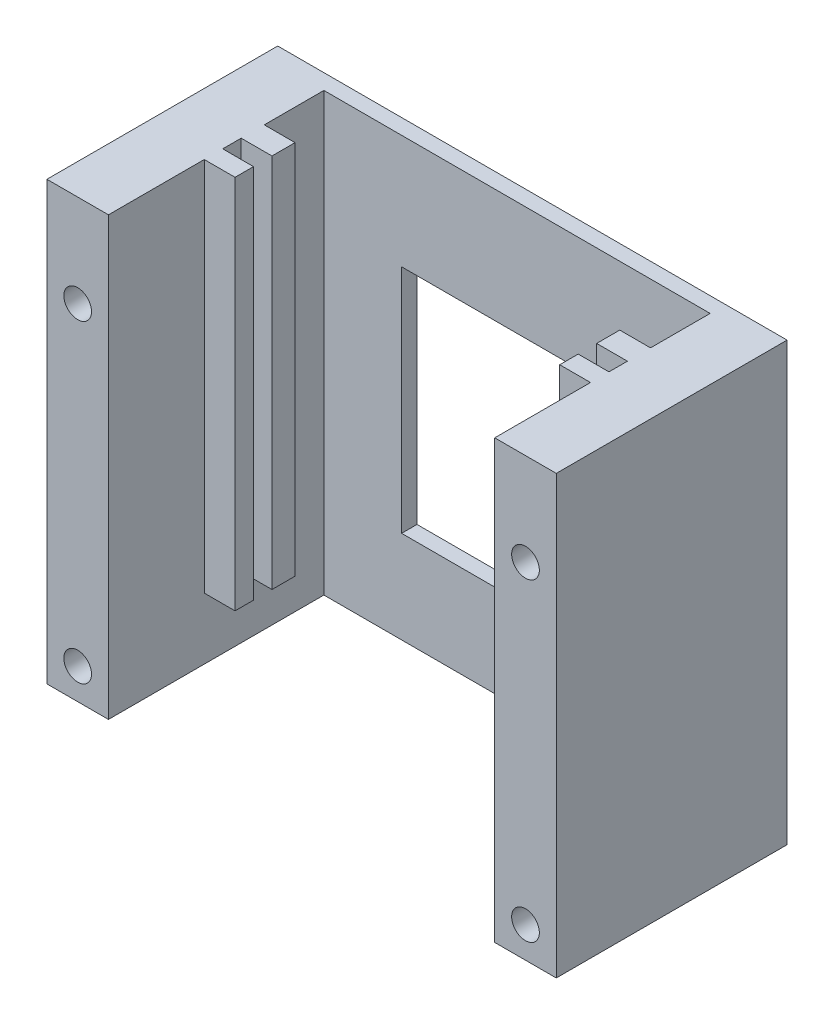
SolidWorks part; units mm, degrees
ref_plane "Plan de face" through (0, 0, 0) normal (0, 0, 1) x (1, 0, 0)
ref_plane "Plan de dessus" through (0, 0, 0) normal (0, 1, 0) x (1, 0, 0)
ref_plane "Plan de droite" through (0, 0, 0) normal (1, 0, 0) x (0, 0, -1)
sketch "Esquisse1" plane through (0, 0, 0) normal (0, 0, 1) x (1, 0, 0)
  line L0 (0, 0) -> (0, -27) construction
  line L1 (0, -27) -> (0, 30) construction
  line L2 (0, 0) -> (25.4165, -15.9375) construction
  line L3 (25.4165, -15.9375) -> (-22.8748, 14.3437) construction
  line L4 (-25.4165, -15.9375) -> (0, 0) construction
  line L5 (0, 0) -> (22.8748, 14.3437) construction
  line L6 (0, 30) -> (25.4165, -15.9375) construction
  line L8 (12.5, -14) -> (-12.5, -14)
  line L9 (12.5, -14) -> (12.5, -17)
  line L10 (12.5, -17) -> (-12.5, -17)
  line L11 (-12.5, -14) -> (-12.5, -17)
  circle A0 centre (0, 0) radius 37
  circle A1 centre (0, 30) radius 1.5
  circle A2 centre (-22.8748, 14.3437) radius 1.5
  circle A3 centre (-25.4165, -15.9375) radius 1.5
  circle A4 centre (0, -27) radius 1.5
  circle A5 centre (25.4165, -15.9375) radius 1.5
  circle A6 centre (22.8748, 14.3437) radius 1.5
  dimension "D1" = 74
  dimension "D11" = 3
  dimension "D12" = 3
  dimension "D13" = 3
  dimension "D14" = 3
  dimension "D15" = 3
  dimension "D16" = 3
  dimension "D2" = 27
  dimension "D3" = 57
  dimension "D4" = 57
  dimension "D5" = 30
  dimension "D6" = 30
  dimension "D7" = 27
  dimension "D8" = 52.5
  dimension "D9" = 52.5
  dimension "D10" = 47.25
  dimension "D17" = 25
  dimension "D18" = 3
  dimension "D19" = 10
  dimension "D20" = 12.5
extrude "Boss.-Extru.1" add sketch "Esquisse1" along normal blind 2
sketch "Esquisse2" plane through (0, 0, 0) normal (0, 0, -1) x (-1, 0, 0)
  line L0 (-16.55, 14.9) -> (-16.55, -13.5)
  line L1 (-12.55, 14.9) -> (12.55, 14.9)
  line L2 (-12.55, 14.9) -> (-12.55, -9.5)
  line L3 (-12.55, -9.5) -> (12.55, -9.5)
  line L4 (12.55, 14.9) -> (12.55, -9.5)
  line L5 (-16.55, -13.5) -> (16.55, -13.5)
  line L6 (16.55, -13.5) -> (16.55, 14.9)
  line L7 (16.55, 14.9) -> (12.55, 14.9)
  line L8 (-16.55, 14.9) -> (-12.55, 14.9)
  point P0 (0, 0)
  dimension "D1" = 25.1
  dimension "D2" = 9.5
  dimension "D3" = 24.4
  dimension "D4" = 4
  dimension "D5" = 4
  dimension "D6" = 4
  dimension "D7" = 12.55
extrude "Boss.-Extru.2" add sketch "Esquisse2" along normal blind 15 contours L8 L0 L5 L6 L7 L4 L3 L2 region at (14.55, 14.4639, 0)
sketch "Esquisse3" plane through (-12.55, 0, 0) normal (1, 0, 0) x (0, 0, -1)
  line L0 (15, 14.9) -> (0, 14.9) construction
  line L1 (10.125, 14.9) -> (8.625, 14.9)
  line L2 (10.125, 14.9) -> (10.125, -13.5)
  line L3 (10.125, -13.5) -> (8.625, -13.5)
  line L4 (8.625, 14.9) -> (8.625, -13.5)
  line L5 (15, -13.5) -> (0, -13.5) construction
  line L6 (0, 14.9) -> (7.5, 14.9) construction
  line L8 (6.225, 14.9) -> (7.425, 14.9)
  line L9 (6.225, 14.9) -> (6.225, -13.5)
  line L10 (6.225, -13.5) -> (7.425, -13.5)
  line L11 (7.425, 14.9) -> (7.425, -13.5)
  line L12 (8, 14.9) -> (8, -13.5) construction
  dimension "D1" = 1.5
  dimension "D2" = 0.625
  dimension "D3" = 1.2
  dimension "D4" = 1.2
  dimension "D5" = 0.575
  dimension "D6" = 0.5
extrude "Boss.-Extru.3" add sketch "Esquisse3" along normal blind 2 contours L11 L10 L9 L8 | L2 L3 L4 L1
sketch "Esquisse5" plane through (12.55, 0, 0) normal (-1, 0, 0) x (0, 0, 1)
  line L1 (-10.125, 14.9) -> (-8.625, 14.9)
  line L2 (-10.125, 14.9) -> (-10.125, -9.5)
  line L3 (-10.125, -9.5) -> (-8.625, -9.5)
  line L4 (-8.625, 14.9) -> (-8.625, -9.5)
  line L5 (-7.425, 14.9) -> (-6.225, 14.9)
  line L6 (-7.425, 14.9) -> (-7.425, -9.5)
  line L7 (-7.425, -9.5) -> (-6.225, -9.5)
  line L8 (-6.225, 14.9) -> (-6.225, -9.5)
extrude "Boss.-Extru.4" add sketch "Esquisse5" along normal blind 2
sketch "Esquisse7" plane through (0, 0, -15) normal (0, 0, -1) x (-1, 0, 0)
  line L1 (-16.55, 14.9) -> (16.55, 14.9)
  line L2 (-16.55, 14.9) -> (-16.55, -13.5)
  line L3 (-16.55, -13.5) -> (16.55, -13.5)
  line L4 (16.55, 14.9) -> (16.55, -13.5)
extrude "Boss.-Extru.5" add sketch "Esquisse7" against normal blind 1
sketch "Esquisse8" plane through (0, 0, -15) normal (0, 0, -1) x (-1, 0, 0)
  line L1 (-7.5, 7.5) -> (7.5, 7.5)
  line L2 (-7.5, 7.5) -> (-7.5, -7.5)
  line L3 (-7.5, -7.5) -> (7.5, -7.5)
  line L4 (7.5, 7.5) -> (7.5, -7.5)
  line L5 (-7.5, 7.5) -> (7.5, -7.5) construction
  line L6 (-7.5, -7.5) -> (7.5, 7.5) construction
  point P0 (0, 0)
  dimension "D1" = 15
  dimension "D2" = 15
extrude "Enlèv. mat.-Extru.1" cut sketch "Esquisse8" against normal blind 3 contours L3 L4 L1 L2
sketch "Esquisse9" plane through (0, -13.5, 0) normal (0, -1, 0) x (1, 0, 0)
  line L0 (16.55, 0) -> (-16.55, 0) construction
  line L1 (-10.5, -4.4) -> (10.5, -4.4)
  line L2 (-10.5, -4.4) -> (-10.5, -6.9)
  line L3 (-10.5, -6.9) -> (10.5, -6.9)
  line L4 (10.5, -4.4) -> (10.5, -6.9)
  line L6 (10.5, -4.4) -> (10.5, 0) construction
  line L7 (10.5, 0) -> (-10.5, 0) construction
  line L8 (-10.5, 0) -> (-10.5, -4.4) construction
  point P6 (0, -4.4)
  dimension "D1" = 21
  dimension "D2" = 2.5
  dimension "D3" = 4.4
  dimension "D4" = 0
extrude "Enlèv. mat.-Extru.2" cut sketch "Esquisse9" against normal up to surface (4 mm away) contours L1 L4 L3 L2 up to face at (0, -9.5, -7.88)
sketch "Esquisse10" plane through (0, 0, 2) normal (0, 0, 1) x (1, 0, 0)
  line L0 (16.55, -13.5) -> (-16.55, -13.5) construction
  line L1 (-16.55, -13.5) -> (-16.55, 14.9) construction
  line L2 (16.55, 14.9) -> (16.55, -13.5) construction
  line L3 (16.55, 14.9) -> (12.55, 14.9) construction
  line L4 (-16.55, 14.9) -> (-12.55, 14.9) construction
  circle A0 centre (-14.55, 8.9) radius 0.9
  circle A1 centre (-14.55, -11.5) radius 0.9
  circle A2 centre (14.55, -11.5) radius 0.9
  circle A3 centre (14.55, 8.9) radius 0.9
  dimension "D1" = 1.8
  dimension "D2" = 1.8
  dimension "D3" = 1.8
  dimension "D4" = 1.8
  dimension "D5" = 2
  dimension "D6" = 2
  dimension "D7" = 2
  dimension "D8" = 2
  dimension "D9" = 2
  dimension "D10" = 6
  dimension "D11" = 6
  dimension "D12" = 2
extrude "Enlèv. mat.-Extru.3" cut sketch "Esquisse10" against normal blind 19
sketch "Esquisse11" plane through (0, 0, 2) normal (0, 0, 1) x (1, 0, 0)
  circle A0 centre (0, 0) radius 37
extrude "Enlèv. mat.-Extru.4" cut sketch "Esquisse11" against normal blind 2
sketch "Sketch1" plane through (0, 0, -15) normal (0, 0, -1) x (-1, 0, 0)
  line L0 (7.5, 7.5) -> (-7.5, -7.5)
  line L1 (-7.5, -7.5) -> (-7.5, 7.5)
  line L2 (-7.5, 7.5) -> (7.5, -7.5)
  point P4 (0, 0)
sketch "Esquisse12" plane through (0, 0, 0) normal (0, 1, 0) x (1, 0, 0)
  line L0 (16.55, 0) -> (-16.55, 0) construction
  line L1 (-12.55, 0) -> (12.55, 0)
  line L2 (-12.55, 0) -> (-12.55, 14)
  line L3 (-12.55, 14) -> (12.55, 14)
  line L4 (12.55, 0) -> (12.55, 14)
  line L5 (16.55, 15) -> (16.55, 0) construction
  line L6 (-16.55, 15) -> (-16.55, 0) construction
  line L7 (16.55, 15) -> (-16.55, 15) construction
  dimension "D1" = 4
  dimension "D2" = 4
  dimension "D3" = 1
sketch "Esquisse13" plane through (0, -13.5, 0) normal (0, -1, 0) x (1, 0, 0)
  line L1 (-12.55, 0) -> (12.55, 0)
  line L2 (-12.55, 0) -> (-12.55, -14)
  line L3 (-12.55, -14) -> (12.55, -14)
  line L4 (12.55, 0) -> (12.55, -14)
extrude "Enlèv. mat.-Extru.5" cut sketch "Esquisse13" against normal blind 4
